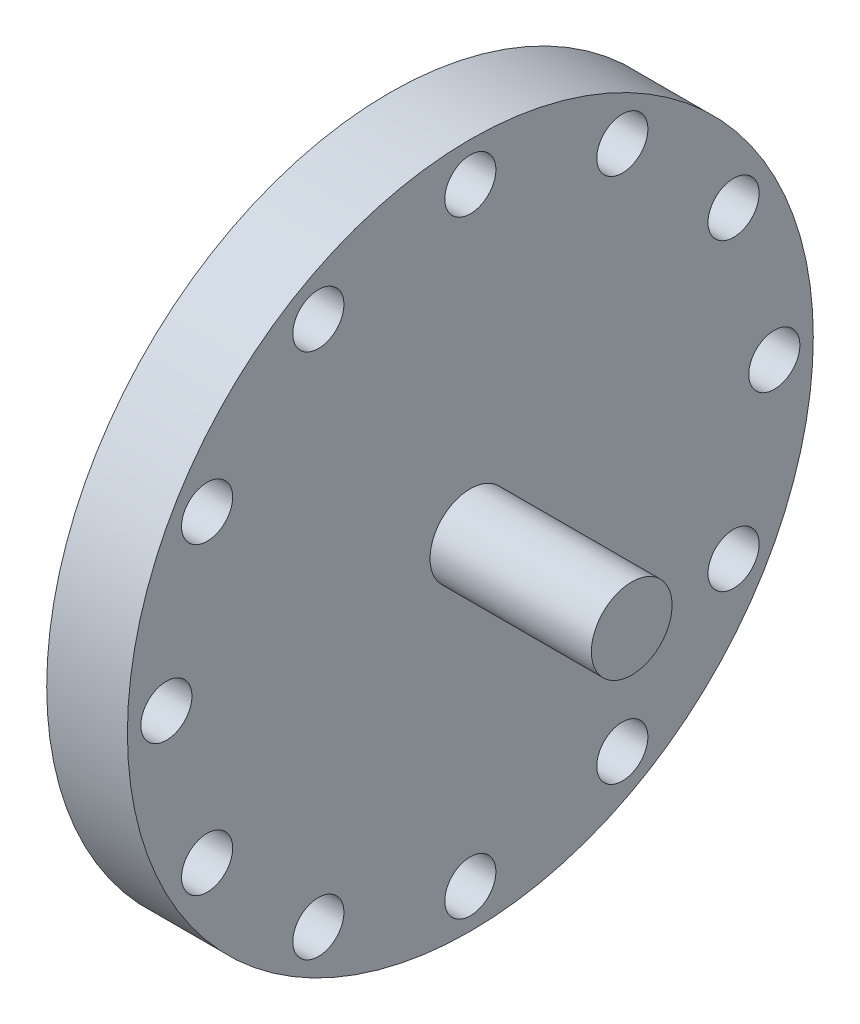
SolidWorks part; units mm, degrees
ref_plane "Спереди" through (0, 0, 0) normal (0, 0, 1) x (1, 0, 0)
ref_plane "Сверху" through (0, 0, 0) normal (0, 1, 0) x (1, 0, 0)
ref_plane "Справа" through (0, 0, 0) normal (1, 0, 0) x (0, 0, -1)
sketch "Эскиз1" plane through (0, 0, 0) normal (0, 0, 1) x (1, 0, 0)
  line L0 (0, 0) -> (100, 0)
  line L1 (0, 0) -> (0, 20)
  line L2 (0, 20) -> (10, 20)
  line L3 (10, 20) -> (10, 127.5)
  line L4 (10, 127.5) -> (40, 127.5)
  line L5 (40, 127.5) -> (40, 15)
  line L6 (40, 15) -> (100, 15)
  line L7 (100, 0) -> (100, 15)
revolve "Повернуть1" add sketch "Эскиз1" angle 360 about L0
sketch "Эскиз2" plane through (0, 0, 0) normal (1, 0, 0) x (0, 0, -1)
  circle A0 centre (0, 0) radius 4.25
extrude "Вырез-Вытянуть1" cut sketch "Эскиз2" along normal blind 20
thread "Резьба1" pitch 1.5 method cut profile "Профиль резьбы1" start angle 0, offset 0, length 20, pitch 1.5, diameter 8.5
ref_plane "Плоскость4" through (0, 0, -4.25) normal (0, -1, 0) x (0, 0, -1)
sketch "Профиль резьбы1" plane through (0, 0, -4.25) normal (0, -1, 0) x (0, 0, -1)
  line L0 (0, 0) -> (0, 1.5) construction
  line L1 (0, 0) -> (0.8119, 0.4687)
  line L2 (0.8119, 0.4687) -> (0.8119, 0.6562)
  line L3 (0.8119, 0.6562) -> (0, 1.125)
  line L4 (0.8119, 0.5625) -> (0, 0.5625) construction
  line L11 (0, 0) -> (0, 1.125)
  point P2 (0, 0)
  dimension "Pitch" = 1.5
  dimension "Profile_Angle" = 60
  dimension "Profile_Land" = 0.1875
  dimension "Profile_Height" = 0.8119
sketch "Эскиз5" plane through (0, 0, 0) normal (1, 0, 0) x (0, 0, -1)
  circle A0 centre (0, 113) radius 9.5
extrude "Вырез-Вытянуть2" cut sketch "Эскиз5" along normal through all
sketch "Эскиз6" plane through (0, 0, 0) normal (1, 0, 0) x (0, 0, -1)
  circle A0 centre (-56.5, 97.8609) radius 9.5
extrude "Вырез-Вытянуть3" cut sketch "Эскиз6" along normal through all
sketch "Эскиз7" plane through (0, 0, 0) normal (1, 0, 0) x (0, 0, -1)
  circle A0 centre (-97.8609, 56.5) radius 9.5
extrude "Вырез-Вытянуть4" cut sketch "Эскиз7" along normal through all
sketch "Эскиз8" plane through (0, 0, 0) normal (1, 0, 0) x (0, 0, -1)
  circle A0 centre (-113, 0) radius 9.5
extrude "Вырез-Вытянуть5" cut sketch "Эскиз8" along normal through all
sketch "Эскиз9" plane through (0, 0, 0) normal (1, 0, 0) x (0, 0, -1)
  circle A0 centre (-97.8609, -56.5) radius 9.5
extrude "Вырез-Вытянуть6" cut sketch "Эскиз9" along normal through all
sketch "Эскиз10" plane through (0, 0, 0) normal (1, 0, 0) x (0, 0, -1)
  circle A0 centre (-56.5, -97.8609) radius 9.5
extrude "Вырез-Вытянуть7" cut sketch "Эскиз10" along normal through all
sketch "Эскиз11" plane through (0, 0, 0) normal (1, 0, 0) x (0, 0, -1)
  circle A0 centre (0, -113) radius 9.5
extrude "Вырез-Вытянуть8" cut sketch "Эскиз11" along normal through all
sketch "Эскиз12" plane through (0, 0, 0) normal (1, 0, 0) x (0, 0, -1)
  circle A0 centre (56.5, -97.8609) radius 9.5
extrude "Вырез-Вытянуть9" cut sketch "Эскиз12" along normal through all
sketch "Эскиз13" plane through (0, 0, 0) normal (1, 0, 0) x (0, 0, -1)
  circle A0 centre (97.8609, -56.5) radius 9.5
extrude "Вырез-Вытянуть10" cut sketch "Эскиз13" along normal through all
sketch "Эскиз14" plane through (0, 0, 0) normal (1, 0, 0) x (0, 0, -1)
  circle A0 centre (113, 0) radius 9.5
extrude "Вырез-Вытянуть11" cut sketch "Эскиз14" along normal through all
sketch "Эскиз15" plane through (0, 0, 0) normal (1, 0, 0) x (0, 0, -1)
  circle A0 centre (97.8609, 56.5) radius 9.5
extrude "Вырез-Вытянуть12" cut sketch "Эскиз15" along normal through all
sketch "Эскиз16" plane through (0, 0, 0) normal (1, 0, 0) x (0, 0, -1)
  circle A0 centre (56.5, 97.8609) radius 9.5
extrude "Вырез-Вытянуть13" cut sketch "Эскиз16" along normal through all
